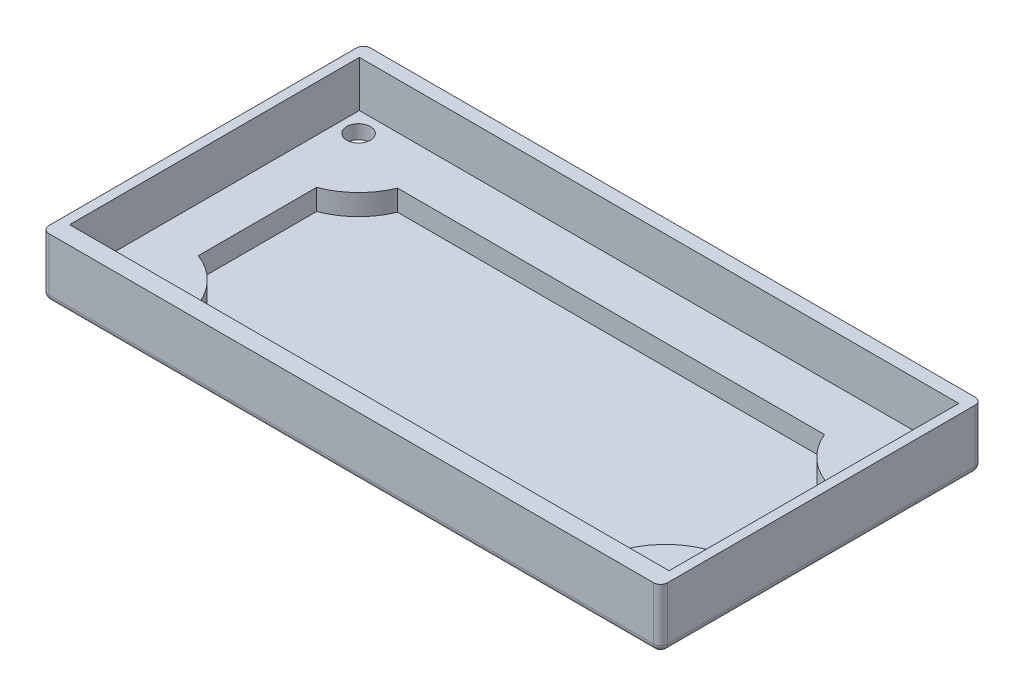
SolidWorks part; units mm, degrees
ref_plane "Alzado" through (0, 0, 0) normal (0, 0, 1) x (1, 0, 0)
ref_plane "Planta" through (0, 0, 0) normal (0, 1, 0) x (1, 0, 0)
ref_plane "Vista lateral" through (0, 0, 0) normal (1, 0, 0) x (0, 0, -1)
sketch "Top-cover-sketch-01" plane through (0, 0, 0) normal (0, 1, 0) x (1, 0, 0)
  line L1 (-22.185, 11.53) -> (22.185, 11.53)
  line L2 (-22.185, 11.53) -> (-22.185, -11.53)
  line L3 (-22.185, -11.53) -> (22.185, -11.53)
  line L4 (22.185, 11.53) -> (22.185, -11.53)
  line L5 (-22.185, 11.53) -> (22.185, -11.53) construction
  line L6 (-22.185, -11.53) -> (22.185, 11.53) construction
  line L7 (-20.105, -9.1) -> (20.105, -9.1) construction
  line L8 (-20.105, -9.1) -> (-20.105, 9.1) construction
  line L9 (-20.105, 9.1) -> (20.105, 9.1) construction
  line L10 (20.105, -9.1) -> (20.105, 9.1) construction
  line L11 (-20.105, -9.1) -> (20.105, 9.1) construction
  line L12 (-20.105, 9.1) -> (20.105, -9.1) construction
  line L13 (-16.0258, 8.1) -> (16.0258, 8.1)
  line L15 (-16.0258, -8.1) -> (16.0258, -8.1)
  line L16 (19.255, 4.9869) -> (19.255, -4.9869)
  line L24 (-19.255, -4.9869) -> (-19.255, 4.9869)
  circle A0 centre (-20.105, 9.1) radius 0.85
  circle A1 centre (20.105, 9.1) radius 0.85
  circle A2 centre (20.105, -9.1) radius 0.85
  circle A3 centre (-20.105, -9.1) radius 0.85
  arc A4 (19.255, -4.9869) -> (16.0258, -8.1) centre (20.105, -9.1) ccw
  arc A5 (16.0258, 8.1) -> (19.255, 4.9869) centre (20.105, 9.1) ccw
  arc A6 (-19.255, 4.9869) -> (-16.0258, 8.1) centre (-20.105, 9.1) ccw
  arc A7 (-19.255, -4.9869) -> (-16.0258, -8.1) centre (-20.105, -9.1) cw
  point P0 (0, 0)
  point P6 (0, 0)
  dimension "D5" = 1.7
  dimension "D1" = 23.06
  dimension "D2" = 44.37
  dimension "D3" = 18.2
  dimension "D4" = 40.21
  dimension "D6" = 2.93
  dimension "D9" = 3.43
  dimension "D15" = 2.93
extrude "Top-cover-ext-shape" add sketch "Top-cover-sketch-01" along normal blind 4.3 contours L3 L4 L1 L2
extrude "Saliente-Extruir1" add sketch "Top-cover-sketch-01<18>" against normal blind 1.5 contours L24 A7 L15 A4 L16 A5 L13 A6 region at (0, 0, 0)
sketch "Top-cover-sketch-01<18>" plane through (0, 0, 0) normal (0, 1, 0) x (1, 0, 0) same geometry as "Top-cover-sketch-01"
shell "Vaciado1" thickness 1 removed face at (0, 4.3, 0)
sketch "Croquis1" plane through (0, -1.5, 0) normal (0, -1, 0) x (1, 0, 0)
  circle A0 centre (-11.8789, 0) radius 3.25
  circle A1 centre (-11.8789, 0) radius 5
extrude "Cortar-Extruir1" cut sketch "Croquis1" against normal blind 0.7 contours A0 region at (-11.8789, -1.5, 0)
extrude "Cortar-Extruir2" cut sketch "Croquis1<5>" against normal blind 0.5 contours A1 A0 region at (-16.7375, -1.5, 0)
sketch "Croquis1<5>" plane through (0, -1.5, 0) normal (0, -1, 0) x (1, 0, 0) same geometry as "Croquis1"
sketch "Croquis2" plane through (0, -0.8, 0) normal (0, -1, 0) x (1, 0, 0)
  line L0 (-22.185, -11.53) -> (-22.185, 11.53) construction
  circle A0 centre (-11.8789, 0) radius 3
extrude "Saliente-Extruir2" add sketch "Croquis2" along normal blind 3.7
fillet "Redondeo1" radius 0.5 8 edges at (22.185, 2.15, 11.53) (22.185, 2.15, -11.53) (-22.185, 0, 0) (22.185, 0, 0) (0, 0, 11.53) (-22.185, 2.15, 11.53) (-22.185, 2.15, -11.53) (0, 0, -11.53)
fillet "Redondeo2" radius 0.3 17 edges at (-11.8789, -1.5, -5) (-19.255, -0.75, -4.9869) (-16.0258, -0.75, -8.1) (-17.19, -1.5, -6.0763) (-19.255, -1.5, 0) (-19.255, -0.75, 4.9869) (-16.0258, -0.75, 8.1) (-17.19, -1.5, 6.0763) (19.255, -0.75, -4.9869) (16.0258, -0.75, -8.1) (19.255, -0.75, 4.9869) (16.0258, -0.75, 8.1) (0, -1.5, -8.1) (17.19, -1.5, -6.0763) (19.255, -1.5, 0) (17.19, -1.5, 6.0763) (0, -1.5, 8.1)
fillet "Chaflán1" radius 0.3 1 edges at (-11.8789, -4.5, -3) type face fillet profile chamfer first side face at (-11.8789, -4.5, -3) second side face at (-11.8789, -4.5, -3)
extrude "Cortar-Extruir3" cut sketch "Top-cover-sketch-01<19>" along normal up to surface (1 mm away) contours A0 | A3 | A1 | A2 up to face at (0, 1, -0.16)
sketch "Top-cover-sketch-01<19>" plane through (0, 0, 0) normal (0, 1, 0) x (1, 0, 0) same geometry as "Top-cover-sketch-01"
